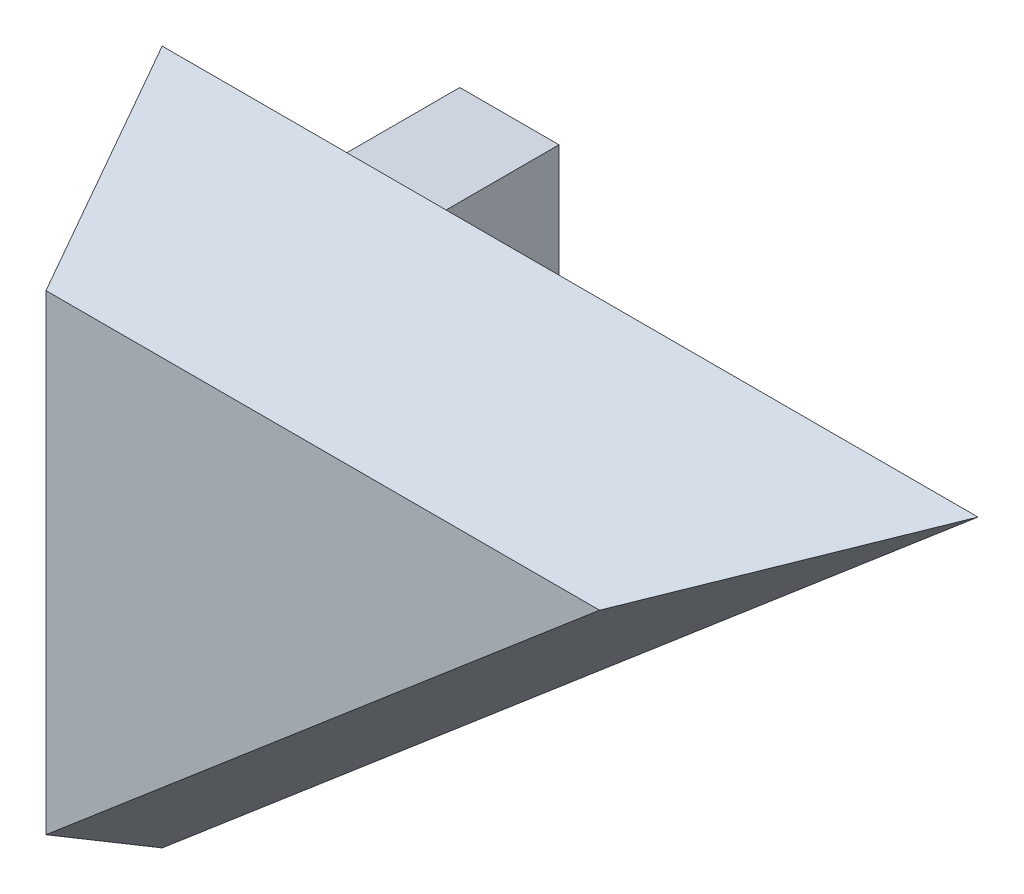
SolidWorks part; units mm, degrees
material "PET"
ref_plane "Front Plane" through (0, 0, 0) normal (0, 0, 1) x (1, 0, 0)
ref_plane "Top Plane" through (0, 0, 0) normal (0, 1, 0) x (1, 0, 0)
ref_plane "Right Plane" through (0, 0, 0) normal (1, 0, 0) x (0, 0, -1)
sketch "Sketch1" plane through (0, 0, 0) normal (0, 0, 1) x (1, 0, 0)
  line L0 (46.355, 33.9725) -> (46.355, 45.085)
  line L1 (46.355, 45.085) -> (59.4101, 45.085)
  line L2 (59.4101, 45.085) -> (46.355, 33.9725)
  dimension "D1" = 11.1125
  dimension "D2" = 13.0551
extrude "Boss-Extrude1" add sketch "Sketch1" along normal blind 2.54
chamfer "Chamfer1" distance 2.54 angle 15 1 edges at (46.355, 39.5288, 2.54) first distance on face at (46.355, 39.5288, 1.27)
chamfer "Chamfer2" distance 2.54 angle 35 1 edges at (53.2228, 45.085, 2.54) first distance on face at (53.0527, 45.085, 1.27)
chamfer "Chamfer3" distance 2.54 angle 20 1 edges at (52.1781, 38.9291, 2.54) first distance on face at (52.5303, 39.2289, 1.27)
sketch "Sketch2" plane through (0, 0, 0) normal (0, 0, -1) x (-1, 0, 0)
  line L0 (-48.7363, 35.9994) -> (-46.355, 35.9994) construction
  line L4 (-47.9425, 37.3672) -> (-49.53, 37.3672)
  line L5 (-47.9425, 37.3672) -> (-47.9425, 43.7172)
  line L6 (-47.9425, 43.7172) -> (-49.53, 43.7172)
  line L7 (-49.53, 37.3672) -> (-49.53, 43.7172)
  line L8 (-47.9425, 37.3672) -> (-49.53, 43.7172) construction
  line L9 (-47.9425, 43.7172) -> (-49.53, 37.3672) construction
  line L10 (-46.355, 33.9725) -> (-59.4101, 45.085) construction
  line L11 (-46.355, 45.085) -> (-46.355, 33.9725) construction
  line L12 (-48.7363, 35.9994) -> (-48.7363, 45.085) construction
  line L13 (-59.4101, 45.085) -> (-46.355, 45.085) construction
  point P6 (-48.7363, 40.5422)
  point P15 (-48.9981, 40.88)
  point P16 (0, 0)
  dimension "D1" = 6.35
  dimension "D2" = 1.5875
  dimension "D3" = 1.5875
extrude "Boss-Extrude2" add sketch "Sketch2" along normal blind 3.175
